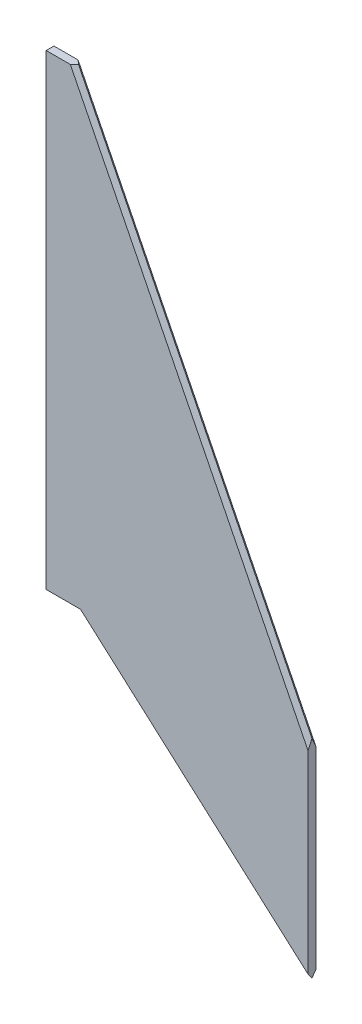
SolidWorks part; units mm, degrees
ref_plane "Front Plane" through (0, 0, 0) normal (0, 0, 1) x (1, 0, 0)
ref_plane "Top Plane" through (0, 0, 0) normal (0, 1, 0) x (1, 0, 0)
ref_plane "Right Plane" through (0, 0, 0) normal (1, 0, 0) x (0, 0, -1)
sketch "Sketch1" plane through (0, 0, 0) normal (0, 0, 1) x (1, 0, 0)
  line L0 (0, 0) -> (0, 180)
  line L1 (0, 180) -> (90, 0)
  line L2 (90, 0) -> (90, -80)
  line L3 (90, -80) -> (0, 0)
  line L5 (0, 0) -> (-11, 0)
  line L6 (0, 0) -> (0, 180)
  line L7 (0, 180) -> (-11, 180)
  line L8 (-11, 0) -> (-11, 180)
  dimension "D1" = 180
  dimension "D2" = 80
  dimension "D3" = 180
  dimension "D4" = 90
  dimension "D5" = 11
extrude "Boss-Extrude1" add sketch "Sketch1" along normal mid plane 3 contours L3 L2 L1 L0 | L8 L5 L0 L7 region at (-5.5, 90, 0) region at (39.2308, 33.3333, 0)
chamfer "Chamfer1" distance 1.5 angle 45 2 edges at (45, 90, -1.5) (45, 90, 1.5)
chamfer "Chamfer2" distance 1.5 angle 45 2 edges at (45, -40, 1.5) (45, -40, -1.5)
